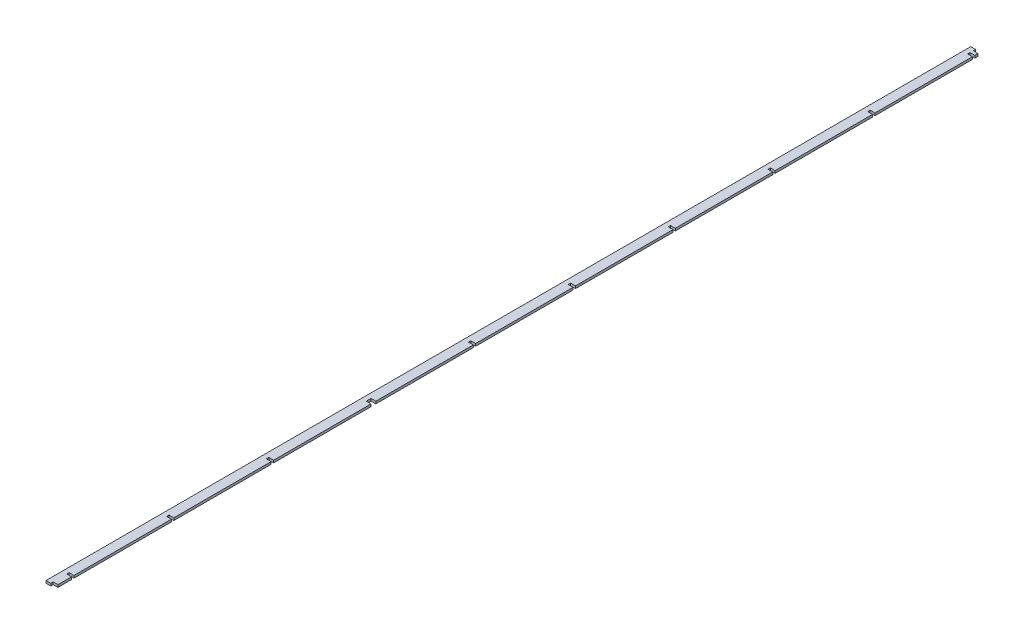
SolidWorks part; units mm, degrees
material "轻木"
ref_plane "前视基准面" through (0, 0, 0) normal (0, 0, 1) x (1, 0, 0)
ref_plane "上视基准面" through (0, 0, 0) normal (0, 1, 0) x (1, 0, 0)
ref_plane "右视基准面" through (0, 0, 0) normal (1, 0, 0) x (0, 0, -1)
other "Configuration Table"
sketch "草图1" plane through (0, 0, 0) normal (0, 0, 1) x (1, 0, 0)
  line L0 (-137.1255, -1006.8019) -> (-137.1255, 48993.1981) construction
  line L1 (-136.0466, -5.3019) -> (-131.1255, -5.3019) construction
  line L2 (-137.1255, -5.3019) -> (-125.1255, -5.3019)
  line L3 (-137.1255, -5.3019) -> (-137.1255, -8.3019)
  line L4 (-137.1255, -8.3019) -> (-125.1255, -8.3019)
  line L5 (-125.1255, -5.3019) -> (-125.1255, -8.3019)
  dimension "D1" = 12
  dimension "D2" = 3
extrude "凸台-拉伸1" add sketch "草图1" along normal blind 1158
sketch "草图3" plane through (0, -5.3019, 0) normal (0, 1, 0) x (1, 0, 0)
  line L0 (-125.1255, -1158) -> (-125.1255, 0) construction
  line L1 (-125.1255, 0) -> (-131.1255, 0)
  line L2 (-125.1255, 0) -> (-125.1255, -3.01)
  line L3 (-125.1255, -3.01) -> (-131.1255, -3.01)
  line L4 (-131.1255, 0) -> (-131.1255, -3.01)
  line L9 (-125.1255, -135.01) -> (-131.1255, -135.01)
  line L34 (-125.1255, -10.01) -> (-131.1255, -10.01)
  line L35 (-125.1255, -760.01) -> (-125.1255, -757.01)
  line L52 (-131.1255, -763.01) -> (-125.1255, -763.01)
  line L59 (-131.1255, -763.01) -> (-131.1255, -760.01)
  line L60 (-125.1255, -135.01) -> (-125.1255, -132.01)
  line L63 (-131.1255, -760.01) -> (-125.1255, -760.01)
  line L65 (-125.1255, -10.01) -> (-125.1255, -7.01)
  line L66 (-125.1255, -7.01) -> (-131.1255, -7.01)
  line L67 (-131.1255, -10.01) -> (-131.1255, -7.01)
  line L68 (-125.1255, -132.01) -> (-131.1255, -132.01)
  line L69 (-131.1255, -135.01) -> (-131.1255, -132.01)
  line L70 (-125.1255, -260.01) -> (-131.1255, -260.01)
  line L71 (-125.1255, -260.01) -> (-125.1255, -257.01)
  line L72 (-125.1255, -257.01) -> (-131.1255, -257.01)
  line L73 (-131.1255, -260.01) -> (-131.1255, -257.01)
  line L74 (-125.1255, -385.01) -> (-131.1255, -385.01)
  line L75 (-125.1255, -385.01) -> (-125.1255, -382.01)
  line L76 (-125.1255, -382.01) -> (-131.1255, -382.01)
  line L77 (-131.1255, -385.01) -> (-131.1255, -382.01)
  line L78 (-125.1255, -510.01) -> (-131.1255, -510.01)
  line L79 (-125.1255, -510.01) -> (-125.1255, -507.01)
  line L80 (-125.1255, -507.01) -> (-131.1255, -507.01)
  line L81 (-131.1255, -510.01) -> (-131.1255, -507.01)
  line L82 (-125.1255, -635.01) -> (-131.1255, -635.01)
  line L83 (-125.1255, -635.01) -> (-125.1255, -632.01)
  line L84 (-125.1255, -632.01) -> (-131.1255, -632.01)
  line L85 (-131.1255, -635.01) -> (-131.1255, -632.01)
  line L86 (-125.1255, -10.01) -> (-125.1255, -135.01) construction
  line L87 (-125.1255, -763.01) -> (-125.1255, -760.01)
  line L88 (-125.1255, -757.01) -> (-131.1255, -757.01)
  line L89 (-131.1255, -757.01) -> (-131.1255, -760.01)
  line L90 (-131.1255, -885.01) -> (-125.1255, -885.01)
  line L91 (-131.1255, -888.01) -> (-131.1255, -885.01)
  line L92 (-131.1255, -888.01) -> (-125.1255, -888.01)
  line L93 (-125.1255, -888.01) -> (-125.1255, -885.01)
  line L94 (-131.1255, -1010.01) -> (-125.1255, -1010.01)
  line L95 (-131.1255, -1013.01) -> (-131.1255, -1010.01)
  line L96 (-131.1255, -1013.01) -> (-125.1255, -1013.01)
  line L97 (-125.1255, -1013.01) -> (-125.1255, -1010.01)
  line L98 (-131.1255, -760.01) -> (-131.1255, -885.01) construction
  line L99 (-131.1255, -1135.01) -> (-125.1255, -1135.01)
  line L100 (-131.1255, -1138.01) -> (-131.1255, -1135.01)
  line L101 (-131.1255, -1138.01) -> (-125.1255, -1138.01)
  line L102 (-125.1255, -1138.01) -> (-125.1255, -1135.01)
  line L104 (-131.1255, -1155.01) -> (-125.1255, -1155.01)
  line L105 (-131.1255, -1155.01) -> (-131.1255, -1158)
  line L106 (-131.1255, -1158) -> (-125.1255, -1158)
  line L107 (-125.1255, -1155.01) -> (-125.1255, -1158)
  line M3 (-125.1255, 0) -> (-137.1255, 0)
  line M5 (-137.1255, -1158) -> (-125.1255, -1158)
  line M6 (-125.1255, -1158) -> (-125.1255, 0)
  dimension "D1" = 125
  dimension "D3" = 4
  dimension "D2" = 125
extrude "切除-拉伸1" cut sketch "草图3" against normal through all contours L4 L3 M3 M6 | L67 L34 L66 M6 | L69 L9 L68 M6 | L73 L70 L72 M6 | L77 L74 L76 M6 | L81 L78 L80 M6 | L85 L82 L84 M6 | L88 L89 L63 M6 | L63 L59 L52 M6 | L91 L92 L90 M6 | L95 L96 L94 M6 | L100 L101 L99 M6 | L104 L105 M5 M6 region at (-128.1255, -5.3019, 1.505) region at (-128.1255, -5.3019, 1156.505) region at (-128.1255, -5.3019, 1136.51) region at (-128.1255, -5.3019, 1011.51) region at (-128.1255, -5.3019, 886.51) region at (-128.1255, -5.3019, 758.51) region at (-128.1255, -5.3019, 633.51) region at (-128.1255, -5.3019, 508.51) region at (-128.1255, -5.3019, 383.51) region at (-128.1255, -5.3019, 258.51) region at (-128.1255, -5.3019, 133.51) region at (-128.1255, -5.3019, 8.51) region at (-128.1255, -5.3019, 761.51)
